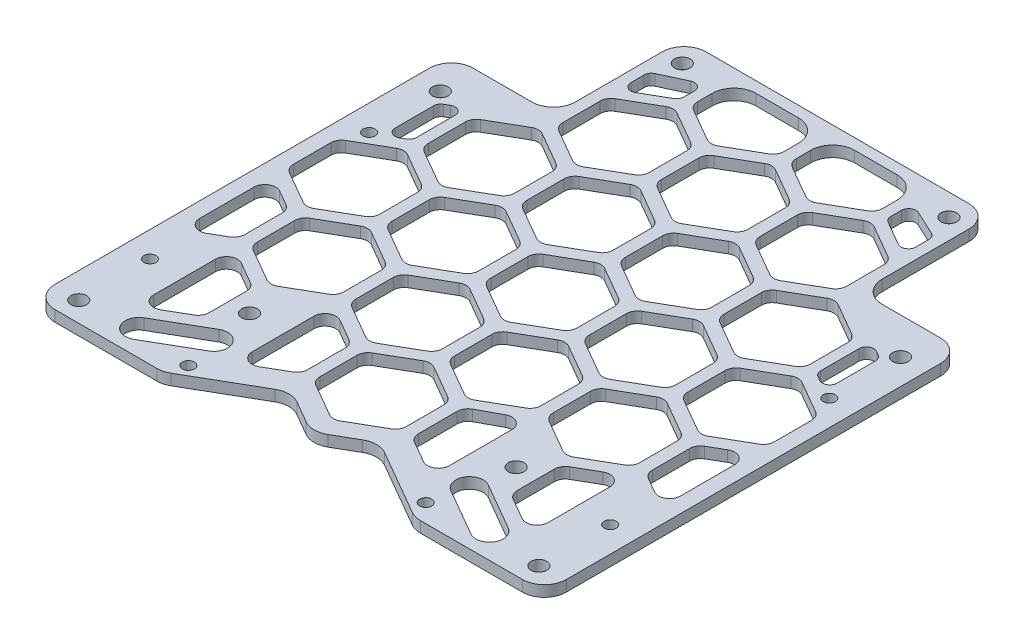
SolidWorks part; units mm, degrees
material "A-玻璃纤维"
ref_plane "前视基准面" through (0, 0, 0) normal (0, 0, 1) x (1, 0, 0)
ref_plane "上视基准面" through (0, 0, 0) normal (0, 1, 0) x (1, 0, 0)
ref_plane "右视基准面" through (0, 0, 0) normal (1, 0, 0) x (0, 0, -1)
other "Configuration Table"
sketch "草图1" plane through (0, 0, 0) normal (0, 1, 0) x (1, 0, 0)
  line L0 (-70, 55) -> (-70, 105)
  line L1 (-59.25, -36.5) -> (59.25, -36.5) construction
  line L2 (-59.25, -36.5) -> (-59.25, 36.5) construction
  line L3 (-59.25, 36.5) -> (59.25, 36.5) construction
  line L4 (59.25, -36.5) -> (59.25, 36.5) construction
  line L5 (-59.25, -36.5) -> (59.25, 36.5) construction
  line L6 (-59.25, 36.5) -> (59.25, -36.5) construction
  line L7 (-63, -49.5) -> (63, -49.5) construction
  line L8 (-63, -49.5) -> (-63, 49.5) construction
  line L9 (-63, 49.5) -> (63, 49.5) construction
  line L10 (63, -49.5) -> (63, 49.5) construction
  line L11 (-63, -49.5) -> (63, 49.5) construction
  line L12 (-63, 49.5) -> (63, -49.5) construction
  line L13 (-70, -55) -> (70, -55)
  line L14 (-70, -55) -> (-70, 55)
  line L15 (-70, 55) -> (70, 55) construction
  line L16 (70, -55) -> (70, 55)
  line L17 (-70, -55) -> (70, 55) construction
  line L18 (-70, 55) -> (70, -55) construction
  line L19 (-70, 105) -> (70, 105)
  line L20 (70, 105) -> (70, 55)
  line L21 (0, 0) -> (0, 30) construction
  line L23 (-36.5, -29.25) -> (36.5, -29.25) construction
  line L24 (-36.5, -29.25) -> (-36.5, 89.25) construction
  line L25 (-36.5, 89.25) -> (36.5, 89.25) construction
  line L26 (36.5, -29.25) -> (36.5, 89.25) construction
  line L27 (-36.5, -29.25) -> (36.5, 89.25) construction
  line L28 (-36.5, 89.25) -> (36.5, -29.25) construction
  circle A0 centre (-59.25, 36.5) radius 1.65 construction
  circle A1 centre (59.25, 36.5) radius 1.65 construction
  circle A2 centre (59.25, -36.5) radius 1.65 construction
  circle A3 centre (-59.25, -36.5) radius 1.65 construction
  circle A4 centre (-63, 49.5) radius 2.15
  circle A5 centre (63, 49.5) radius 2.15
  circle A6 centre (63, -49.5) radius 2.15
  circle A7 centre (-63, -49.5) radius 2.15
  circle A8 centre (-36.5, 89.25) radius 2.15
  circle A9 centre (36.5, 89.25) radius 2.15
  circle A10 centre (36.5, -29.25) radius 2.15
  circle A11 centre (-36.5, -29.25) radius 2.15
  point P0 (0, 0)
  point P10 (0, 0)
  point P19 (0, 0)
  dimension "D3" = 3.3
  dimension "D6" = 4.3
  dimension "D1" = 118.5
  dimension "D2" = 73
  dimension "D4" = 126
  dimension "D5" = 99
  dimension "D7" = 140
  dimension "D8" = 110
  dimension "D9" = 50
  dimension "D10" = 73
  dimension "D11" = 118.5
  dimension "D12" = 30
extrude "凸台-拉伸1" add sketch "草图1" along normal blind 3
sketch "草图3" plane through (0, 3, 0) normal (0, 1, 0) x (1, 0, 0)
  line L0 (-70, -50) -> (70, -50) construction
  line L1 (-70, 105) -> (-70, -55) construction
  line L2 (70, -55) -> (70, 105) construction
  line L3 (-70, -55) -> (70, -55) construction
  line L4 (0, 0) -> (0, 105) construction
  line L5 (70, 105) -> (-70, 105) construction
  circle A0 centre (-32.5, -50) radius 1.65
  circle A1 centre (32.5, -50) radius 1.65
  dimension "D2" = 65
  dimension "D3" = 3.3
  dimension "D1" = 5
extrude "切除-拉伸1" cut sketch "草图3" against normal through all
sketch "草图4" plane through (0, 3, 0) normal (0, 1, 0) x (1, 0, 0)
  line L2 (-63, -30) -> (63, -30) construction
  line L3 (-63, -30) -> (-63, 30) construction
  line L4 (-63, 30) -> (63, 30) construction
  line L5 (63, -30) -> (63, 30) construction
  line L6 (-63, -30) -> (63, 30) construction
  line L7 (-63, 30) -> (63, -30) construction
  circle A1 centre (-63, 30) radius 1.65
  circle A2 centre (-63, -30) radius 1.65
  circle A3 centre (63, -30) radius 1.65
  circle A4 centre (63, 30) radius 1.65
  dimension "D4" = 3.3
  dimension "D1" = 60
  dimension "D2" = 126
extrude "切除-拉伸2" cut sketch "草图4" against normal through all
sketch "草图5" plane through (0, 3, 0) normal (0, 1, 0) x (1, 0, 0)
  line L1 (-70, 105) -> (-46.5, 105)
  line L2 (-70, 105) -> (-70, 59.5)
  line L3 (-70, 59.5) -> (-46.5, 59.5)
  line L4 (-46.5, 105) -> (-46.5, 59.5)
  line L5 (70, 105) -> (46.5, 105)
  line L6 (70, 105) -> (70, 59.5)
  line L7 (70, 59.5) -> (46.5, 59.5)
  line L8 (46.5, 105) -> (46.5, 59.5)
  circle A0 centre (-36.5, 89.25) radius 2.15 construction
  circle A1 centre (-63, 49.5) radius 2.15 construction
  circle A2 centre (36.5, 89.25) radius 2.15 construction
  circle A3 centre (63, 49.5) radius 2.15 construction
  dimension "D1" = 10
  dimension "D2" = 10
  dimension "D3" = 10
  dimension "D4" = 10
extrude "切除-拉伸3" cut sketch "草图5" against normal through all
fillet "圆角1" [suppressed] radius 5
sketch "草图6" plane through (0, 3, 0) normal (0, 1, 0) x (1, 0, 0)
  line L1 (-54, 77.6543) -> (-65.825, 70.8272) construction
  line L2 (-65.825, 70.8272) -> (-65.825, 57.1728) construction
  line L3 (-65.825, 57.1728) -> (-54, 50.3457) construction
  line L4 (-54, 50.3457) -> (-42.175, 57.1728) construction
  line L5 (-42.175, 57.1728) -> (-42.175, 70.8272) construction
  line L6 (-42.175, 70.8272) -> (-54, 77.6543) construction
  line L7 (46.5, 105) -> (-46.5, 105) construction
  line L8 (-27, 77.6543) -> (-38.825, 70.8272)
  line L9 (-38.825, 70.8272) -> (-38.825, 57.1728)
  line L10 (-38.825, 57.1728) -> (-27, 50.3457)
  line L11 (-27, 50.3457) -> (-15.175, 57.1728)
  line L12 (-15.175, 57.1728) -> (-15.175, 70.8272)
  line L13 (-15.175, 70.8272) -> (-27, 77.6543)
  line L14 (0, 77.6543) -> (-11.825, 70.8272) construction
  line L15 (-11.825, 70.8272) -> (-11.825, 57.1728) construction
  line L16 (-11.825, 57.1728) -> (0, 50.3457) construction
  line L17 (0, 50.3457) -> (11.825, 57.1728) construction
  line L18 (11.825, 57.1728) -> (11.825, 70.8272) construction
  line L19 (11.825, 70.8272) -> (0, 77.6543) construction
  line L20 (27, 77.6543) -> (15.175, 70.8272) construction
  line L21 (15.175, 70.8272) -> (15.175, 57.1728) construction
  line L22 (15.175, 57.1728) -> (27, 50.3457) construction
  line L23 (27, 50.3457) -> (38.825, 57.1728) construction
  line L24 (38.825, 57.1728) -> (38.825, 70.8272) construction
  line L25 (38.825, 70.8272) -> (27, 77.6543) construction
  line L26 (54, 77.6543) -> (42.175, 70.8272) construction
  line L27 (42.175, 70.8272) -> (42.175, 57.1728) construction
  line L28 (42.175, 57.1728) -> (54, 50.3457) construction
  line L29 (54, 50.3457) -> (65.825, 57.1728) construction
  line L30 (65.825, 57.1728) -> (65.825, 70.8272) construction
  line L31 (65.825, 70.8272) -> (54, 77.6543) construction
  line L32 (-54, 77.6543) -> (-27, 77.6543) construction
  line L33 (-54, 64) -> (-48.0875, 74.2408) construction
  line L34 (-13.5, 101.037) -> (-25.325, 94.2099)
  line L35 (-25.325, 94.2099) -> (-25.325, 80.5555)
  line L36 (-25.325, 80.5555) -> (-13.5, 73.7284)
  line L37 (-13.5, 73.7284) -> (-1.675, 80.5555)
  line L38 (-1.675, 80.5555) -> (-1.675, 94.2099)
  line L39 (-1.675, 94.2099) -> (-13.5, 101.037)
  line L40 (-27, 77.6543) -> (-13.5, 101.037) construction
  line L41 (-54, 64) -> (-59.9125, 74.2408) construction
  line L42 (13.5, 101.037) -> (1.675, 94.2099)
  line L43 (1.675, 94.2099) -> (1.675, 80.5555)
  line L44 (1.675, 80.5555) -> (13.5, 73.7284)
  line L45 (13.5, 73.7284) -> (25.325, 80.5555)
  line L46 (25.325, 80.5555) -> (25.325, 94.2099)
  line L47 (25.325, 94.2099) -> (13.5, 101.037)
  line L48 (27, 77.6543) -> (13.5, 101.037) construction
  line L49 (-40.5, 54.2716) -> (-52.325, 47.4445)
  line L50 (-52.325, 47.4445) -> (-52.325, 33.7901)
  line L51 (-52.325, 33.7901) -> (-40.5, 26.963)
  line L52 (-40.5, 26.963) -> (-28.675, 33.7901)
  line L53 (-28.675, 33.7901) -> (-28.675, 47.4445)
  line L54 (-28.675, 47.4445) -> (-40.5, 54.2716)
  line L55 (-27, 77.6543) -> (-40.5, 54.2716) construction
  line L56 (-54, 30.8843) -> (-65.825, 24.0572)
  line L57 (-65.825, 24.0572) -> (-65.825, 10.4028)
  line L58 (-65.825, 10.4028) -> (-54, 3.5757)
  line L59 (-54, 3.5757) -> (-42.175, 10.4028)
  line L60 (-42.175, 10.4028) -> (-42.175, 24.0572)
  line L61 (-42.175, 24.0572) -> (-54, 30.8843)
  line L62 (-54, -15.8857) -> (-65.825, -22.7128) construction
  line L63 (-65.825, -22.7128) -> (-65.825, -36.3672) construction
  line L64 (-65.825, -36.3672) -> (-54, -43.1943) construction
  line L65 (-54, -43.1943) -> (-42.175, -36.3672) construction
  line L66 (-42.175, -36.3672) -> (-42.175, -22.7128) construction
  line L67 (-42.175, -22.7128) -> (-54, -15.8857) construction
  line L68 (-27, 30.8843) -> (-38.825, 24.0572)
  line L69 (-38.825, 24.0572) -> (-38.825, 10.4028)
  line L70 (-38.825, 10.4028) -> (-27, 3.5757)
  line L71 (-27, 3.5757) -> (-15.175, 10.4028)
  line L72 (-15.175, 10.4028) -> (-15.175, 24.0572)
  line L73 (-15.175, 24.0572) -> (-27, 30.8843)
  line L74 (-27, -15.8857) -> (-38.825, -22.7128) construction
  line L75 (-38.825, -22.7128) -> (-38.825, -36.3672) construction
  line L76 (-38.825, -36.3672) -> (-27, -43.1943) construction
  line L77 (-27, -43.1943) -> (-15.175, -36.3672) construction
  line L78 (-15.175, -36.3672) -> (-15.175, -22.7128) construction
  line L79 (-15.175, -22.7128) -> (-27, -15.8857) construction
  line L80 (0, 30.8843) -> (-11.825, 24.0572)
  line L81 (-11.825, 24.0572) -> (-11.825, 10.4028)
  line L82 (-11.825, 10.4028) -> (0, 3.5757)
  line L83 (0, 3.5757) -> (11.825, 10.4028)
  line L84 (11.825, 10.4028) -> (11.825, 24.0572)
  line L85 (11.825, 24.0572) -> (0, 30.8843)
  line L86 (0, -15.8857) -> (-11.825, -22.7128)
  line L87 (-11.825, -22.7128) -> (-11.825, -36.3672)
  line L88 (-11.825, -36.3672) -> (0, -43.1943)
  line L89 (0, -43.1943) -> (11.825, -36.3672)
  line L90 (11.825, -36.3672) -> (11.825, -22.7128)
  line L91 (11.825, -22.7128) -> (0, -15.8857)
  line L92 (27, 30.8843) -> (15.175, 24.0572)
  line L93 (15.175, 24.0572) -> (15.175, 10.4028)
  line L94 (15.175, 10.4028) -> (27, 3.5757)
  line L95 (27, 3.5757) -> (38.825, 10.4028)
  line L96 (38.825, 10.4028) -> (38.825, 24.0572)
  line L97 (38.825, 24.0572) -> (27, 30.8843)
  line L98 (27, -15.8857) -> (15.175, -22.7128) construction
  line L99 (15.175, -22.7128) -> (15.175, -36.3672) construction
  line L100 (15.175, -36.3672) -> (27, -43.1943) construction
  line L101 (27, -43.1943) -> (38.825, -36.3672) construction
  line L102 (38.825, -36.3672) -> (38.825, -22.7128) construction
  line L103 (38.825, -22.7128) -> (27, -15.8857) construction
  line L104 (54, 30.8843) -> (42.175, 24.0572)
  line L105 (42.175, 24.0572) -> (42.175, 10.4028)
  line L106 (42.175, 10.4028) -> (54, 3.5757)
  line L107 (54, 3.5757) -> (65.825, 10.4028)
  line L108 (65.825, 10.4028) -> (65.825, 24.0572)
  line L109 (65.825, 24.0572) -> (54, 30.8843)
  line L110 (54, -15.8857) -> (42.175, -22.7128) construction
  line L111 (42.175, -22.7128) -> (42.175, -36.3672) construction
  line L112 (42.175, -36.3672) -> (54, -43.1943) construction
  line L113 (54, -43.1943) -> (65.825, -36.3672) construction
  line L114 (65.825, -36.3672) -> (65.825, -22.7128) construction
  line L115 (65.825, -22.7128) -> (54, -15.8857) construction
  line L116 (-27, 77.6543) -> (-38.825, 70.8272) construction
  line L117 (-38.825, 70.8272) -> (-38.825, 57.1728) construction
  line L118 (-38.825, 57.1728) -> (-27, 50.3457) construction
  line L119 (-27, 50.3457) -> (-15.175, 57.1728) construction
  line L120 (-15.175, 57.1728) -> (-15.175, 70.8272) construction
  line L121 (-15.175, 70.8272) -> (-27, 77.6543) construction
  line L122 (0, 77.6543) -> (-11.825, 70.8272)
  line L123 (-11.825, 70.8272) -> (-11.825, 57.1728)
  line L124 (-11.825, 57.1728) -> (0, 50.3457)
  line L125 (0, 50.3457) -> (11.825, 57.1728)
  line L126 (11.825, 57.1728) -> (11.825, 70.8272)
  line L127 (11.825, 70.8272) -> (0, 77.6543)
  line L128 (27, 77.6543) -> (15.175, 70.8272)
  line L129 (15.175, 70.8272) -> (15.175, 57.1728)
  line L130 (15.175, 57.1728) -> (27, 50.3457)
  line L131 (27, 50.3457) -> (38.825, 57.1728)
  line L132 (38.825, 57.1728) -> (38.825, 70.8272)
  line L133 (38.825, 70.8272) -> (27, 77.6543)
  line L134 (54, 77.6543) -> (42.175, 70.8272) construction
  line L135 (42.175, 70.8272) -> (42.175, 57.1728) construction
  line L136 (42.175, 57.1728) -> (54, 50.3457) construction
  line L137 (54, 50.3457) -> (65.825, 57.1728) construction
  line L138 (65.825, 57.1728) -> (65.825, 70.8272) construction
  line L139 (65.825, 70.8272) -> (54, 77.6543) construction
  line L140 (-54, 77.6543) -> (-54, 30.8843) construction
  line L141 (-54, 77.6543) -> (-27, 77.6543) construction
  line L142 (-13.5, 54.2716) -> (-25.325, 47.4445)
  line L143 (-25.325, 47.4445) -> (-25.325, 33.7901)
  line L144 (-25.325, 33.7901) -> (-13.5, 26.963)
  line L145 (-13.5, 26.963) -> (-1.675, 33.7901)
  line L146 (-1.675, 33.7901) -> (-1.675, 47.4445)
  line L147 (-1.675, 47.4445) -> (-13.5, 54.2716)
  line L148 (13.5, 54.2716) -> (1.675, 47.4445)
  line L149 (1.675, 47.4445) -> (1.675, 33.7901)
  line L150 (1.675, 33.7901) -> (13.5, 26.963)
  line L151 (13.5, 26.963) -> (25.325, 33.7901)
  line L152 (25.325, 33.7901) -> (25.325, 47.4445)
  line L153 (25.325, 47.4445) -> (13.5, 54.2716)
  line L154 (40.5, 54.2716) -> (28.675, 47.4445)
  line L155 (28.675, 47.4445) -> (28.675, 33.7901)
  line L156 (28.675, 33.7901) -> (40.5, 26.963)
  line L157 (40.5, 26.963) -> (52.325, 33.7901)
  line L158 (52.325, 33.7901) -> (52.325, 47.4445)
  line L159 (52.325, 47.4445) -> (40.5, 54.2716)
  line L160 (-13.5, 7.5016) -> (-25.325, 0.6745)
  line L161 (-25.325, 0.6745) -> (-25.325, -12.9799)
  line L162 (-25.325, -12.9799) -> (-13.5, -19.807)
  line L163 (-13.5, -19.807) -> (-1.675, -12.9799)
  line L164 (-1.675, -12.9799) -> (-1.675, 0.6745)
  line L165 (-1.675, 0.6745) -> (-13.5, 7.5016)
  line L166 (13.5, 7.5016) -> (1.675, 0.6745)
  line L167 (1.675, 0.6745) -> (1.675, -12.9799)
  line L168 (1.675, -12.9799) -> (13.5, -19.807)
  line L169 (13.5, -19.807) -> (25.325, -12.9799)
  line L170 (25.325, -12.9799) -> (25.325, 0.6745)
  line L171 (25.325, 0.6745) -> (13.5, 7.5016)
  line L172 (40.5, 7.5016) -> (28.675, 0.6745)
  line L173 (28.675, 0.6745) -> (28.675, -12.9799)
  line L174 (28.675, -12.9799) -> (40.5, -19.807)
  line L175 (40.5, -19.807) -> (52.325, -12.9799)
  line L176 (52.325, -12.9799) -> (52.325, 0.6745)
  line L177 (52.325, 0.6745) -> (40.5, 7.5016)
  line L178 (-40.5, 7.5016) -> (-52.325, 0.6745)
  line L179 (-52.325, 0.6745) -> (-52.325, -12.9799)
  line L180 (-52.325, -12.9799) -> (-40.5, -19.807)
  line L181 (-40.5, -19.807) -> (-28.675, -12.9799)
  line L182 (-28.675, -12.9799) -> (-28.675, 0.6745)
  line L183 (-28.675, 0.6745) -> (-40.5, 7.5016)
  line L184 (-40.5, 54.2716) -> (-13.5, 54.2716) construction
  line L185 (-40.5, 54.2716) -> (-40.5, 7.5016) construction
  line L186 (-27, -15.8857) -> (-27, -43.1943)
  line L187 (-27, -43.1943) -> (-15.175, -36.3672)
  line L188 (-15.175, -36.3672) -> (-15.175, -22.7128)
  line L189 (-15.175, -22.7128) -> (-27, -15.8857)
  line L190 (27, -15.8857) -> (27, -43.1943)
  line L191 (27, -43.1943) -> (15.175, -36.3672)
  line L192 (15.175, -36.3672) -> (15.175, -22.2819)
  line L193 (15.175, -22.2819) -> (27, -15.8857)
  line L194 (-54, -15.8857) -> (-54, -43.1943)
  line L195 (-54, -43.1943) -> (-42.175, -36.3672)
  line L196 (-42.175, -36.3672) -> (-42.175, -22.7128)
  line L197 (-54, -15.8857) -> (-42.175, -22.7128)
  line L198 (54, -15.8857) -> (54, -43.1943)
  line L199 (54, -43.1943) -> (42.175, -36.3672)
  line L200 (42.175, -36.3672) -> (42.175, -22.7128)
  line L201 (54, -15.8857) -> (42.175, -22.7128)
  line L202 (55.825, 0.6745) -> (55.825, -12.9799)
  line L203 (55.825, -12.9799) -> (65.825, -18.7534)
  line L204 (65.825, -18.7534) -> (65.825, 6.448)
  line L205 (65.825, 6.448) -> (55.825, 0.6745)
  line L206 (0, -1000) -> (0, 49000) construction
  line L207 (-65.825, -18.7534) -> (-65.825, 6.448)
  line L208 (-55.825, -12.9799) -> (-65.825, -18.7534)
  line L209 (-55.825, 0.6745) -> (-55.825, -12.9799)
  line L210 (-65.825, 6.448) -> (-55.825, 0.6745)
  circle A0 centre (-54, 64) radius 11.825 construction
  point P10 (0, 0)
  dimension "D1" = 23.65
  dimension "D3" = 41
  dimension "D5" = 27
  dimension "D7" = 27
  dimension "D9" = 27
  dimension "D11" = 27
  dimension "D14" = 4
  dimension "D15" = 46.77
  dimension "D16" = 27
  dimension "D18" = 3.5
  dimension "D19" = 27
  dimension "D20" = 46.77
  dimension "D21" = 23.3873
  dimension "D22" = 23.3827
  dimension "D4" = 5
  dimension "D6" = 2
  dimension "D8" = 2
  dimension "D10" = 2
  dimension "D12" = 3
  dimension "D13" = 5
  dimension "D17" = 2
extrude "切除-拉伸4" cut sketch "草图6" against normal through all
fillet "圆角2" radius 3 138 edges at (-15.175, 1.5, -57.1728) (-27, 1.5, -50.3457) (-38.825, 1.5, -57.1728) (-38.825, 1.5, -70.8272) (-27, 1.5, -77.6543) (-15.175, 1.5, -70.8272) (-28.675, 1.5, 12.9799) (-40.5, 1.5, 19.807) (-52.325, 1.5, 12.9799) (-52.325, 1.5, -0.6745) (-40.5, 1.5, -7.5016) (-28.675, 1.5, -0.6745) (52.325, 1.5, 12.9799) (40.5, 1.5, 19.807) (28.675, 1.5, 12.9799) (28.675, 1.5, -0.6745) (40.5, 1.5, -7.5016) (52.325, 1.5, -0.6745) (-15.175, 1.5, -10.4028) (-27, 1.5, -3.5757) (-38.825, 1.5, -10.4028) (-38.825, 1.5, -24.0572) (-27, 1.5, -30.8843) (-15.175, 1.5, -24.0572) (11.825, 1.5, -10.4028) (0, 1.5, -3.5757) (-11.825, 1.5, -10.4028) (-11.825, 1.5, -24.0572) (0, 1.5, -30.8843) (11.825, 1.5, -24.0572) (11.825, 1.5, 36.3672) (0, 1.5, 43.1943) (-11.825, 1.5, 36.3672) (-11.825, 1.5, 22.7128) (0, 1.5, 15.8857) (11.825, 1.5, 22.7128) (38.825, 1.5, -10.4028) (27, 1.5, -3.5757) (15.175, 1.5, -10.4028) (15.175, 1.5, -24.0572) (27, 1.5, -30.8843) (38.825, 1.5, -24.0572) (-42.175, 1.5, -10.4028) (-54, 1.5, -3.5757) (-65.825, 1.5, -10.4028) (-65.825, 1.5, -24.0572) (-54, 1.5, -30.8843) (-42.175, 1.5, -24.0572) (-28.675, 1.5, -33.7901) (-40.5, 1.5, -26.963) (-52.325, 1.5, -33.7901) (-52.325, 1.5, -47.4445) (-40.5, 1.5, -54.2716) (-28.675, 1.5, -47.4445) (25.325, 1.5, -80.5555) (13.5, 1.5, -73.7284) (1.675, 1.5, -80.5555) (1.675, 1.5, -94.2099) (13.5, 1.5, -101.037) (25.325, 1.5, -94.2099) (-1.675, 1.5, -80.5555) (-13.5, 1.5, -73.7284) (-25.325, 1.5, -80.5555) (-25.325, 1.5, -94.2099) (-1.675, 1.5, -94.2099) (25.325, 1.5, 12.9799) (13.5, 1.5, 19.807) (1.675, 1.5, 12.9799) (1.675, 1.5, -0.6745) (13.5, 1.5, -7.5016) (25.325, 1.5, -0.6745) (-1.675, 1.5, 12.9799) (-13.5, 1.5, 19.807) (-25.325, 1.5, 12.9799) (-25.325, 1.5, -0.6745) (-13.5, 1.5, -7.5016) (-1.675, 1.5, -0.6745) (52.325, 1.5, -33.7901) (40.5, 1.5, -26.963) (28.675, 1.5, -33.7901) (28.675, 1.5, -47.4445) (40.5, 1.5, -54.2716) (52.325, 1.5, -47.4445) (25.325, 1.5, -33.7901) (13.5, 1.5, -26.963) (1.675, 1.5, -33.7901) (1.675, 1.5, -47.4445) (13.5, 1.5, -54.2716) (25.325, 1.5, -47.4445) (65.825, 1.5, -10.4028) (54, 1.5, -3.5757) (42.175, 1.5, -10.4028) (42.175, 1.5, -24.0572) (54, 1.5, -30.8843) (65.825, 1.5, -24.0572) (11.825, 1.5, -57.1728) (0, 1.5, -50.3457) (-11.825, 1.5, -57.1728) (-11.825, 1.5, -70.8272) (0, 1.5, -77.6543) (11.825, 1.5, -70.8272) (38.825, 1.5, -57.1728) (27, 1.5, -50.3457) (15.175, 1.5, -57.1728) (15.175, 1.5, -70.8272) (27, 1.5, -77.6543) (38.825, 1.5, -70.8272) (-1.675, 1.5, -33.7901) (-13.5, 1.5, -26.963) (-25.325, 1.5, -33.7901) (-25.325, 1.5, -47.4445) (-13.5, 1.5, -54.2716) (-1.675, 1.5, -47.4445) (-13.5, 1.5, -101.037) (-15.175, 1.5, 36.3672) (-27, 1.5, 43.1943) (-27, 1.5, 15.8857) (-15.175, 1.5, 22.7128) (27, 1.5, 43.1943) (15.175, 1.5, 36.3672) (27, 1.5, 15.8857) (15.175, 1.5, 22.2819) (-65.825, 1.5, -6.448) (-55.825, 1.5, -0.6745) (-55.825, 1.5, 12.9799) (-65.825, 1.5, 18.7534) (-42.175, 1.5, 36.3672) (-54, 1.5, 43.1943) (-54, 1.5, 15.8857) (65.825, 1.5, 18.7534) (55.825, 1.5, 12.9799) (55.825, 1.5, -0.6745) (65.825, 1.5, -6.448) (54, 1.5, 43.1943) (42.175, 1.5, 36.3672) (42.175, 1.5, 22.7128) (54, 1.5, 15.8857) (-42.175, 1.5, 22.7128)
sketch "草图9" plane through (0, 3, 0) normal (0, 1, 0) x (1, 0, 0)
  line L0 (0, -1000) -> (0, 49000) construction
  line L1 (-1000, 0) -> (49000, 0) construction
  line L3 (46.5, 105) -> (-46.5, 105) construction
  line L4 (0, 95.25) -> (-42, 95.25)
  line L5 (-42, 95.25) -> (-42, 59.5)
  line L6 (-42, 59.5) -> (-46.5, 59.5)
  line L7 (-46.5, 59.5) -> (-46.5, 105)
  line L8 (-46.5, 105) -> (0, 105)
  line L10 (46.5, 59.5) -> (46.5, 105)
  line L11 (42, 59.5) -> (46.5, 59.5)
  line L12 (42, 95.25) -> (42, 59.5)
  line L13 (0, 95.25) -> (42, 95.25)
  line L15 (46.5, 105) -> (0, 105)
  line L21 (-34.448, -55) -> (-12, -42.0396)
  line L22 (-70, -55) -> (70, -55) construction
  line L23 (-12, -42.0396) -> (0, -48.9678)
  line L24 (-34.448, -55) -> (34.448, -55)
  line L25 (12, -42.0396) -> (0, -48.9678)
  line L26 (34.448, -55) -> (12, -42.0396)
  line L27 (1.5, -42.3283) -> (10.325, -37.2332) construction
  line L29 (-22.5, -40.5963) -> (-16.675, -37.2332) construction
  line L30 (-55.325, 49.3124) -> (-55.325, 34.1608)
  line L31 (-55.325, 34.1608) -> (-60.5, 31.173)
  line L32 (-60.5, 31.173) -> (-60.5, 46.3246)
  line L33 (-60.5, 46.3246) -> (-55.325, 49.3124)
  line L34 (-55.5, 30.0183) -> (-64.325, 24.9232) construction
  line L35 (-52.325, 45.7124) -> (-52.325, 35.5222) construction
  line L36 (60.5, 31.173) -> (60.5, 46.3246)
  line L37 (55.325, 34.1608) -> (60.5, 31.173)
  line L38 (55.325, 49.3124) -> (55.325, 34.1608)
  line L39 (60.5, 46.3246) -> (55.325, 49.3124)
  circle A0 centre (-36.5, 89.25) radius 2.15 construction
  circle A1 centre (-63, 49.5) radius 2.15 construction
  point P28 (0, -55)
  dimension "D7" = 4
  dimension "D1" = 5
  dimension "D2" = 6
  dimension "D3" = 5.5
  dimension "D4" = 6.5
  dimension "D5" = 3.5
  dimension "D6" = 3
  dimension "D8" = 2.5
extrude "切除-拉伸6" cut sketch "草图9" against normal through all
sketch "草图10" plane through (0, 3, 0) normal (0, 1, 0) x (1, 0, 0)
  line L0 (42, 95.25) -> (42, 59.5) construction
  line L1 (-42, 95.25) -> (42, 95.25)
  line L2 (-42, 95.25) -> (-42, 92.25)
  line L3 (-42, 92.25) -> (42, 92.25)
  line L4 (42, 95.25) -> (42, 92.25)
  dimension "D1" = 3
extrude "凸台-拉伸2" add sketch "草图10" against normal up to surface (3 mm away) up to face at (-57.9125, 0, -40.2427)
fillet "圆角3" radius 6 17 edges at (42, 1.5, -95.25) (42, 1.5, -59.5) (70, 1.5, -59.5) (70, 1.5, 55) (34.448, 1.5, 55) (12, 1.5, 42.0396) (0, 1.5, 48.9678) (-12, 1.5, 42.0396) (-34.448, 1.5, 55) (-70, 1.5, -59.5) (-42, 1.5, -59.5) (-42, 1.5, -95.25) (25.325, 1.5, -92.25) (1.675, 1.5, -92.25) (-1.675, 1.5, -92.25) (-25.325, 1.5, -92.25) (-70, 1.5, 55)
fillet "圆角4" radius 2 8 edges at (55.325, 1.5, -49.3124) (60.5, 1.5, -46.3246) (60.5, 1.5, -31.173) (55.325, 1.5, -34.1608) (-55.325, 1.5, -34.1608) (-60.5, 1.5, -31.173) (-55.325, 1.5, -49.3124) (-60.5, 1.5, -46.3246)
sketch "草图13" plane through (0, 3, 0) normal (0, 1, 0) x (1, 0, 0)
  line L0 (-48, -48) -> (-35.0096, -40.5) construction
  line L1 (-49.875, -44.7524) -> (-36.8846, -37.2524)
  line L2 (-46.125, -51.2476) -> (-33.1346, -43.7476)
  line L3 (0, -1000) -> (0, 49000) construction
  line L4 (48, -48) -> (35.0096, -40.5) construction
  line L5 (49.875, -44.7524) -> (36.8846, -37.2524)
  line L6 (46.125, -51.2476) -> (33.1346, -43.7476)
  line L7 (-64, -55) -> (-36.0557, -55) construction
  line L8 (-70, 53.5) -> (-70, -49) construction
  line L9 (-49.5, -40.5963) -> (-43.675, -37.2332) construction
  line L10 (-39, 82.5673) -> (-39, 74.1902)
  line L11 (-39, 74.1902) -> (-28.325, 80.3534)
  line L12 (-28.325, 80.3534) -> (-28.325, 87.5452)
  line L13 (-28.325, 87.5452) -> (-39, 82.5673)
  line L14 (-28.5, 76.7883) -> (-37.325, 71.6932) construction
  line L15 (-42, 65.5) -> (-42, 89.25) construction
  line L16 (-25.325, 86.25) -> (-25.325, 82.2876) construction
  line L17 (28.325, 80.3534) -> (28.325, 87.5452)
  line L18 (39, 74.1902) -> (28.325, 80.3534)
  line L19 (39, 82.5673) -> (39, 74.1902)
  line L20 (28.325, 87.5452) -> (39, 82.5673)
  arc A0 (-49.875, -44.7524) -> (-46.125, -51.2476) centre (-48, -48) ccw
  arc A1 (-33.1346, -43.7476) -> (-36.8846, -37.2524) centre (-35.0096, -40.5) ccw
  arc A2 (49.875, -44.7524) -> (46.125, -51.2476) centre (48, -48) cw
  arc A3 (33.1346, -43.7476) -> (36.8846, -37.2524) centre (35.0096, -40.5) cw
  circle A4 centre (-36.5, 89.25) radius 2.15 construction
  point P2 (-41.5048, -44.25)
  point P12 (41.5048, -44.25)
  dimension "D4" = 3.75
  dimension "D1" = 7
  dimension "D2" = 22
  dimension "D3" = 15
  dimension "D5" = 3
  dimension "D6" = 3
  dimension "D7" = 3
  dimension "D8" = 5
  dimension "D9" = 115
extrude "切除-拉伸7" cut sketch "草图13" against normal through all
fillet "圆角5" radius 2 8 edges at (28.325, 1.5, -87.5452) (39, 1.5, -82.5673) (39, 1.5, -74.1902) (28.325, 1.5, -80.3534) (-28.325, 1.5, -80.3534) (-39, 1.5, -74.1902) (-39, 1.5, -82.5673) (-28.325, 1.5, -87.5452)
